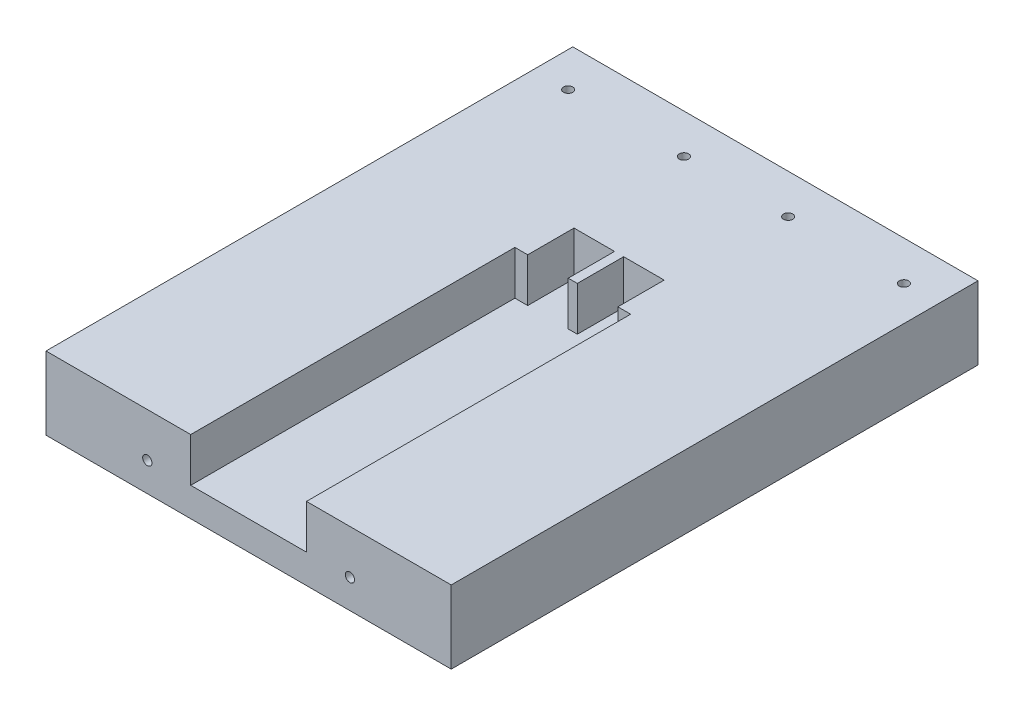
SolidWorks part; units mm, degrees
ref_plane "Front Plane" through (0, 0, 0) normal (0, 0, 1) x (1, 0, 0)
ref_plane "Top Plane" through (0, 0, 0) normal (0, 1, 0) x (1, 0, 0)
ref_plane "Right Plane" through (0, 0, 0) normal (1, 0, 0) x (0, 0, -1)
sketch "Sketch1" plane through (0, 0, 0) normal (0, 1, 0) x (1, 0, 0)
  line L0 (44.45, 115.57) -> (44.45, 0) construction
  line L1 (0, 0) -> (88.9, 0)
  line L2 (0, 0) -> (0, 115.57)
  line L3 (0, 115.57) -> (88.9, 115.57)
  line L4 (88.9, 0) -> (88.9, 115.57)
  line L5 (31.75, 0) -> (57.15, 0)
  line L6 (31.75, 0) -> (31.75, 71.12)
  line L7 (31.75, 71.12) -> (57.15, 71.12)
  line L8 (57.15, 0) -> (57.15, 71.12)
  line L9 (43.45, 71.12) -> (43.45, 0) construction
  line L10 (45.45, 0) -> (45.45, 71.12) construction
  line L12 (43.45, 71.12) -> (34.56, 71.12)
  line L13 (43.45, 71.12) -> (43.45, 81.28)
  line L14 (43.45, 81.28) -> (34.56, 81.28)
  line L15 (34.56, 71.12) -> (34.56, 81.28)
  line L16 (45.45, 71.12) -> (54.34, 71.12)
  line L17 (45.45, 71.12) -> (45.45, 81.28)
  line L18 (45.45, 81.28) -> (54.34, 81.28)
  line L19 (54.34, 71.12) -> (54.34, 81.28)
  point P11 (44.45, 71.12)
  dimension "D1" = 115.57
  dimension "D2" = 88.9
  dimension "D3" = 25.4
  dimension "D4" = 71.12
  dimension "D5" = 1
  dimension "D6" = 1
  dimension "D7" = 8.89
  dimension "D8" = 8.89
  dimension "D9" = 10.16
  dimension "D10" = 10.16
extrude "Boss-Extrude2" add sketch "Sketch1" along normal blind 16.002 contours L19 L7 L8 L1 L4 L3 L2 L6 L15 L14 L13 L17 L18 region at (1.4581, 0, -57.785)
extrude "Boss-Extrude3" add sketch "Sketch1<6>" along normal blind 6.35 separate body contours L1 L8 L7 L6 region at (44.45, 0, -35.56)
sketch "Sketch1<6>" plane through (0, 0, 0) normal (0, 1, 0) x (1, 0, 0) same geometry as "Sketch1"
extrude "Boss-Extrude4" add sketch "Sketch1<7>" along normal blind 6.35 contours L15 L7 L13 L14 | L7 L19 L18 L17 region at (39.005, 0, -76.2) region at (49.895, 0, -76.2)
sketch "Sketch1<7>" plane through (0, 0, 0) normal (0, 1, 0) x (1, 0, 0) same geometry as "Sketch1"
sketch "Sketch2" plane through (0, 0, 0) normal (0, 0, 1) x (1, 0, 0)
  line L0 (0, 6.35) -> (88.9, 6.35) construction
  line L1 (0, 16.002) -> (0, 0) construction
  line L2 (88.9, 16.002) -> (88.9, 0) construction
  line L3 (0, 12.7) -> (88.9, 12.7) construction
  line L4 (0, 0) -> (88.9, 0) construction
  dimension "D1" = 6.35
  dimension "D2" = 6.35
sketch "Sketch3" plane through (0, 16.002, 0) normal (0, 1, 0) x (1, 0, 0)
  line L0 (0, 0) -> (0, 115.57) construction
  line L1 (3.175, 109.22) -> (9.271, 109.22)
  line L2 (3.175, 109.22) -> (3.175, 96.52)
  line L3 (3.175, 96.52) -> (9.271, 96.52)
  line L4 (9.271, 109.22) -> (9.271, 96.52)
  line L5 (3.175, 83.82) -> (9.271, 83.82)
  line L6 (3.175, 83.82) -> (3.175, 71.12)
  line L7 (3.175, 71.12) -> (9.271, 71.12)
  line L8 (9.271, 83.82) -> (9.271, 71.12)
  line L9 (3.175, 58.42) -> (9.271, 58.42)
  line L10 (3.175, 58.42) -> (3.175, 45.72)
  line L11 (3.175, 45.72) -> (9.271, 45.72)
  line L12 (9.271, 58.42) -> (9.271, 45.72)
  line L13 (0, 115.57) -> (88.9, 115.57) construction
  line L15 (3.175, 33.02) -> (9.271, 33.02)
  line L16 (3.175, 33.02) -> (3.175, 20.32)
  line L17 (3.175, 20.32) -> (9.271, 20.32)
  line L18 (9.271, 33.02) -> (9.271, 20.32)
  line L19 (44.45, 115.57) -> (44.45, 0) construction
  line L20 (0, 0) -> (88.9, 0) construction
  line L21 (79.629, 33.02) -> (79.629, 20.32)
  line L22 (85.725, 20.32) -> (79.629, 20.32)
  line L23 (85.725, 33.02) -> (85.725, 20.32)
  line L24 (85.725, 33.02) -> (79.629, 33.02)
  line L25 (79.629, 58.42) -> (79.629, 45.72)
  line L26 (85.725, 45.72) -> (79.629, 45.72)
  line L27 (85.725, 58.42) -> (85.725, 45.72)
  line L28 (85.725, 58.42) -> (79.629, 58.42)
  line L29 (79.629, 83.82) -> (79.629, 71.12)
  line L30 (85.725, 71.12) -> (79.629, 71.12)
  line L31 (85.725, 83.82) -> (85.725, 71.12)
  line L32 (85.725, 83.82) -> (79.629, 83.82)
  line L33 (79.629, 109.22) -> (79.629, 96.52)
  line L34 (85.725, 96.52) -> (79.629, 96.52)
  line L35 (85.725, 109.22) -> (85.725, 96.52)
  line L36 (85.725, 109.22) -> (79.629, 109.22)
  dimension "D1" = 6.096
  dimension "D4" = 12.7
  dimension "D5" = 12.7
  dimension "D6" = 12.7
  dimension "D7" = 3.175
  dimension "D8" = 6.35
  dimension "D9" = 12.7
  dimension "D10" = 12.7
  dimension "D11" = 12.7
  dimension "D13" = 12.7
extrude "Cut-Extrude1" [suppressed] cut sketch "Sketch3" against normal blind 9.652
sketch "Sketch4" plane through (0, 16.002, 0) normal (0, 1, 0) x (1, 0, 0)
  line L0 (0, 0) -> (0, 115.57) construction
  line L1 (88.9, 0) -> (88.9, 115.57) construction
  line L2 (0, 115.57) -> (88.9, 115.57) construction
  circle A0 centre (7.62, 106.934) radius 1.016
  circle A1 centre (33.02, 106.934) radius 1.016
  circle A2 centre (55.88, 106.934) radius 1.016
  circle A3 centre (81.28, 106.934) radius 1.016
  dimension "D1" = 2.032
  dimension "D2" = 2.032
  dimension "D3" = 2.032
  dimension "D4" = 2.032
  dimension "D5" = 7.62
  dimension "D6" = 25.4
  dimension "D7" = 7.62
  dimension "D8" = 25.4
  dimension "D9" = 8.636
extrude "Cut-Extrude2" cut sketch "Sketch4" against normal through all
sketch "Sketch5" plane through (0, 0, 0) normal (0, 0, 1) x (1, 0, 0)
  line L0 (0, 16.002) -> (0, 0) construction
  line L1 (0, 0) -> (88.9, 0) construction
  line L4 (88.9, 16.002) -> (88.9, 0) construction
  circle A0 centre (22.225, 6.35) radius 1.016
  circle A1 centre (66.675, 6.35) radius 1.016
  dimension "D3" = 2.032
  dimension "D4" = 2.032
  dimension "D1" = 22.225
  dimension "D2" = 6.35
  dimension "D5" = 6.35
  dimension "D6" = 22.225
extrude "Cut-Extrude3" cut sketch "Sketch5" against normal blind 12.7
